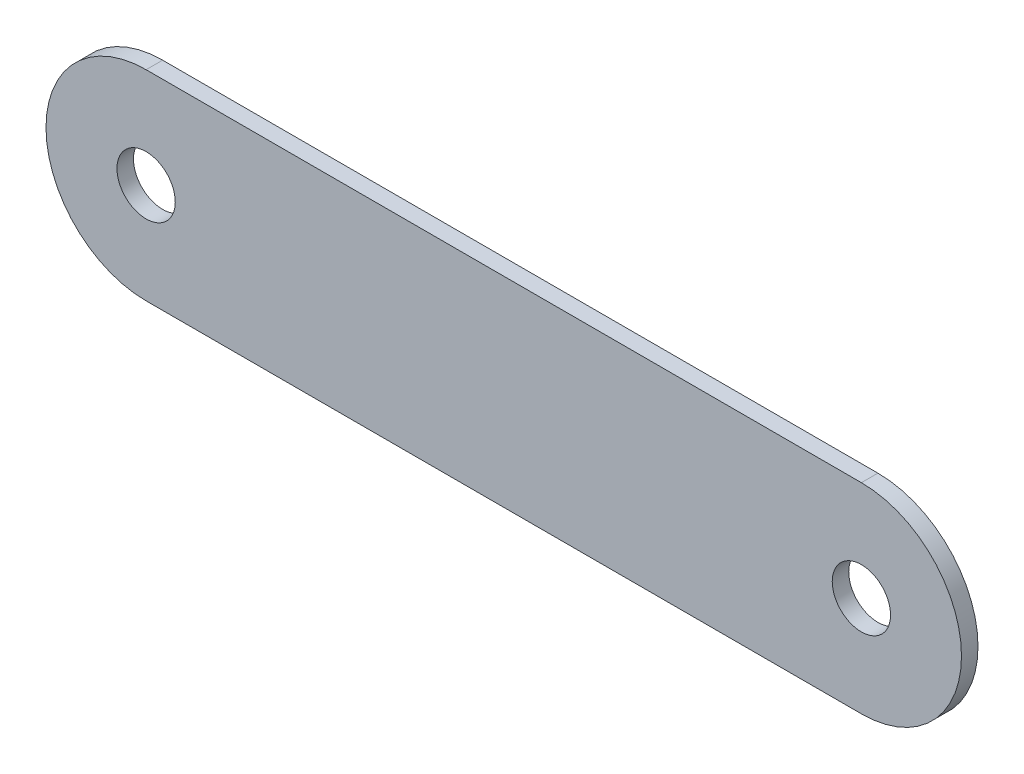
SolidWorks part; units mm, degrees
ref_plane "Front" through (0, 0, 0) normal (0, 0, 1) x (1, 0, 0)
ref_plane "Top" through (0, 0, 0) normal (0, 1, 0) x (1, 0, 0)
ref_plane "Right" through (0, 0, 0) normal (1, 0, 0) x (0, 0, -1)
sketch "Sketch1" plane through (0, 0, 0) normal (0, 0, 1) x (1, 0, 0)
  line L0 (-65, 0) -> (65, 0) construction
  line L1 (-65, 18.193) -> (65, 18.193)
  line L2 (-65, -18.193) -> (65, -18.193)
  arc A0 (-65, 18.193) -> (-65, -18.193) centre (-65, 0) ccw
  arc A1 (65, -18.193) -> (65, 18.193) centre (65, 0) ccw
  circle A2 centre (-65, 0) radius 5.3
  circle A4 centre (65, 0) radius 5.3
  point P2 (65, 0)
  point P3 (0, 0)
  dimension "D1" = 10.6
  dimension "D2" = 18.193
  dimension "D4" = 10.6
  dimension "D3" = 130
extrude "Boss-Extrude1" add sketch "Sketch1" along normal blind 3
